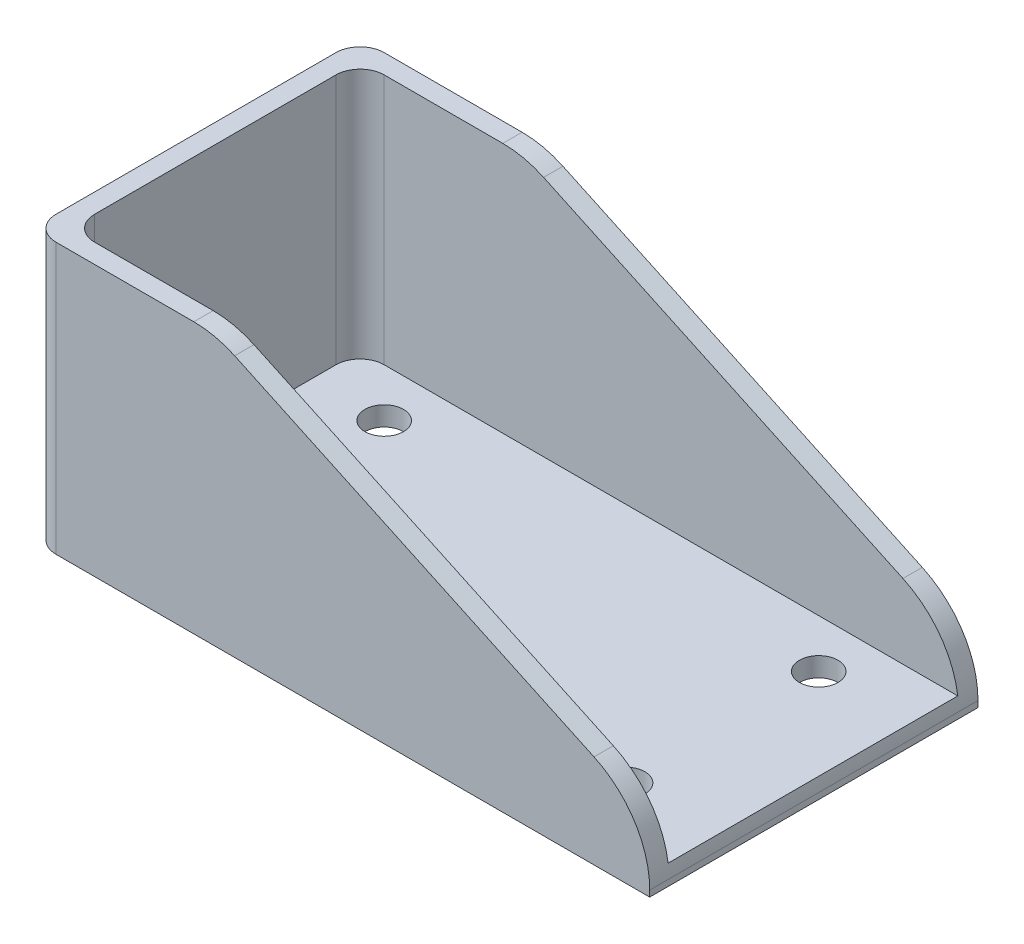
SolidWorks part; units mm, degrees
ref_plane "Front" through (0, 0, 0) normal (0, 0, 1) x (1, 0, 0)
ref_plane "Top" through (0, 0, 0) normal (0, 1, 0) x (1, 0, 0)
ref_plane "Right" through (0, 0, 0) normal (1, 0, 0) x (0, 0, -1)
sketch "Эскиз1" plane through (0, 0, 0) normal (0, 1, 0) x (1, 0, 0)
  line L1 (30, -15) -> (-30, -15)
  line L2 (30, -15) -> (30, 15)
  line L3 (30, 15) -> (-30, 15)
  line L4 (-30, -15) -> (-30, 15)
  line L5 (0, 15) -> (0, -15) construction
  line L6 (30, 0) -> (-30, 0) construction
  point P0 (0, 0)
  dimension "D1" = 60
  dimension "D2" = 30
extrude "Вытянуть-Тонкостенный1" add sketch "Эскиз1" along normal blind 28 thin thin type one direction wall 2
extrude "Бобышка-Вытянуть1" add sketch "Эскиз1<2>" along normal blind 2
sketch "Эскиз1<2>" plane through (0, 0, 0) normal (0, 1, 0) x (1, 0, 0) same geometry as "Эскиз1"
sketch "Эскиз3" plane through (0, 0, 17) normal (0, 0, 1) x (1, 0, 0)
  line L0 (32, 28) -> (32, 0) construction
  line L1 (-32, 0) -> (32, 0)
  line L2 (-32, 0) -> (-32, 2)
  line L3 (-32, 2) -> (32, 2)
  line L4 (32, 0) -> (32, 2)
  line L5 (-32, 2) -> (-32, 28)
  line L6 (32, 2) -> (32, 7)
  line L7 (-32, 28) -> (32, 28) construction
  line L8 (-32, 28) -> (-13, 28)
  line L9 (32, 28) -> (32, 2)
  line L10 (-13, 28) -> (32, 28)
  line L11 (32, 7) -> (-13, 28)
  line M3 (32, 0) -> (32, 28)
  line M4 (32, 28) -> (-32, 28)
  dimension "D1" = 2
  dimension "D2" = 26
  dimension "D3" = 45
  dimension "D4" = 5
fillet "Скругление3" radius 2.5 4 edges at (-32, 14, 17) (-32, 14, -17) (-30, 15, -15) (-30, 15, 15)
extrude "Вырез-Вытянуть6" cut sketch "Эскиз3" against normal through all both and the other way through all contours L11 M3 M4 region at (17, 21, 17)
fillet "Скругление4" radius 10 3 edges at (32, 7, 0)
sketch "Эскиз8" plane through (30, 0, 0) normal (-1, 0, 0) x (0, 0, 1)
  line L0 (15, 6.6314) -> (-15, 6.6314) construction
  line L1 (-15, 2) -> (15, 2)
  line L2 (-15, 2) -> (-15, 6.6314)
  line L3 (-15, 6.6314) -> (15, 6.6314)
  line L4 (15, 2) -> (15, 6.6314)
  line L5 (15, 2) -> (15, 28) construction
extrude "Вырез-Вытянуть7" cut sketch "Эскиз8" against normal through all
sketch "Эскиз9" plane through (0, 2, 0) normal (0, 1, 0) x (1, 0, 0)
  line L1 (22.5, 10) -> (-22.5, 10) construction
  line L2 (22.5, 10) -> (22.5, -10) construction
  line L3 (22.5, -10) -> (-22.5, -10) construction
  line L4 (-22.5, 10) -> (-22.5, -10) construction
  line L5 (0, -10) -> (0, 10) construction
  line L6 (22.5, 0) -> (-22.5, 0) construction
  circle A0 centre (-22.5, -10) radius 2
  circle A1 centre (-22.5, 10) radius 2
  circle A2 centre (22.5, 10) radius 2
  circle A3 centre (22.5, -10) radius 2
  dimension "D3" = 4
  dimension "D1" = 20
  dimension "D2" = 45
extrude "Вырез-Вытянуть9" cut sketch "Эскиз9" against normal through all both and the other way through all contours A3 | A2 | A1 | A0
